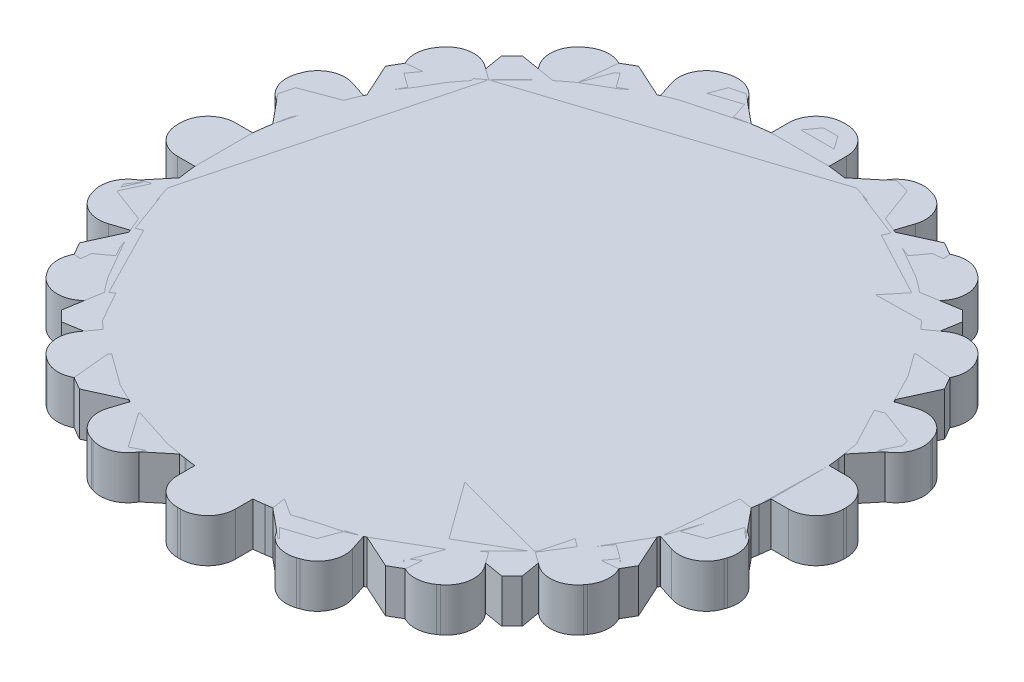
SolidWorks part; units mm, degrees
ref_plane "Front Plane" through (0, 0, 0) normal (0, 0, 1) x (1, 0, 0)
ref_plane "Top Plane" through (0, 0, 0) normal (0, 1, 0) x (1, 0, 0)
ref_plane "Right Plane" through (0, 0, 0) normal (1, 0, 0) x (0, 0, -1)
sketch "Sketch1" plane through (0, 0, 0) normal (0, 1, 0) x (1, 0, 0)
  line L111 (-0.5, 14.7462) -> (0.5, 14.7462)
  line L112 (0.5, 14.7462) -> (2, 12.5441)
  line L113 (-0.5, 14.7462) -> (-2, 12.5441)
  line L114 (6.433, 12.8885) -> (6.631, 10.2315)
  line L115 (5.567, 13.3885) -> (6.433, 12.8885)
  line L116 (5.567, 13.3885) -> (3.1669, 12.2315)
  line L117 (10.6423, 8.3132) -> (9.4853, 5.9131)
  line L118 (10.1423, 9.1792) -> (10.6423, 8.3132)
  line L119 (10.1423, 9.1792) -> (7.4853, 9.3772)
  line L120 (12, 2.2462) -> (9.798, 0.7462)
  line L121 (12, 3.2462) -> (12, 2.2462)
  line L122 (12, 3.2462) -> (9.798, 4.7462)
  line L123 (10.1423, -3.6868) -> (7.4853, -3.8849)
  line L124 (10.6423, -2.8208) -> (10.1423, -3.6868)
  line L125 (10.6423, -2.8208) -> (9.4853, -0.4208)
  line L126 (5.567, -7.8961) -> (3.1669, -6.7391)
  line L127 (6.433, -7.3961) -> (5.567, -7.8961)
  line L128 (6.433, -7.3961) -> (6.631, -4.7391)
  line L129 (-0.5, -9.2538) -> (-2, -7.0518)
  line L130 (0.5, -9.2538) -> (-0.5, -9.2538)
  line L131 (0.5, -9.2538) -> (2, -7.0518)
  line L132 (-6.433, -7.3961) -> (-6.631, -4.7391)
  line L133 (-5.567, -7.8961) -> (-6.433, -7.3961)
  line L134 (-5.567, -7.8961) -> (-3.1669, -6.7391)
  line L135 (-10.6423, -2.8208) -> (-9.4853, -0.4208)
  line L136 (-10.1423, -3.6868) -> (-10.6423, -2.8208)
  line L137 (-10.1423, -3.6868) -> (-7.4853, -3.8849)
  line L138 (-12, 3.2462) -> (-9.798, 4.7462)
  line L139 (-12, 2.2462) -> (-12, 3.2462)
  line L140 (-12, 2.2462) -> (-9.798, 0.7462)
  line L141 (-10.1423, 9.1792) -> (-7.4853, 9.3772)
  line L142 (-10.6423, 8.3132) -> (-10.1423, 9.1792)
  line L143 (-10.6423, 8.3132) -> (-9.4853, 5.9131)
  line L144 (-5.567, 13.3885) -> (-3.1669, 12.2315)
  line L145 (-6.433, 12.8885) -> (-5.567, 13.3885)
  line L146 (-6.433, 12.8885) -> (-6.631, 10.2315)
  arc A43 (-2, 12.5441) -> (-3.1669, 12.2315) centre (0, 2.7462) ccw
  arc A44 (-6.631, 10.2315) -> (-7.4853, 9.3772) centre (0, 2.7462) ccw
  arc A45 (-9.4853, 5.9131) -> (-9.798, 4.7462) centre (0, 2.7462) ccw
  arc A46 (-9.798, 0.7462) -> (-9.4853, -0.4208) centre (0, 2.7462) ccw
  arc A47 (-7.4853, -3.8849) -> (-6.631, -4.7391) centre (0, 2.7462) ccw
  arc A48 (-3.1669, -6.7391) -> (-2, -7.0518) centre (0, 2.7462) ccw
  arc A49 (2, -7.0518) -> (3.1669, -6.7391) centre (0, 2.7462) ccw
  arc A50 (6.631, -4.7391) -> (7.4853, -3.8849) centre (0, 2.7462) ccw
  arc A51 (9.4853, -0.4208) -> (9.798, 0.7462) centre (0, 2.7462) ccw
  arc A52 (9.798, 4.7462) -> (9.4853, 5.9131) centre (0, 2.7462) ccw
  arc A53 (7.4853, 9.3772) -> (6.631, 10.2315) centre (0, 2.7462) ccw
  arc A54 (3.1669, 12.2315) -> (2, 12.5441) centre (0, 2.7462) ccw
  point P6 (0, 0)
  point P8 (0, 0)
  point P9 (0, 0)
  point P12 (0, 2.7462)
  point P17 (0, 0)
  point P18 (0, 2.7462)
  point P22 (-2.5, 0.7462)
  point P63 (0, 0)
  point P68 (0, 0)
  point P69 (0, 2.7462)
  point P119 (0, 0)
  dimension "D1" = 20
  dimension "D8" = 12
sketch "Sketch2" plane through (0, 0, 0) normal (0, 1, 0) x (1, 0, 0)
  line L0 (-2, 0) -> (2, 0)
  line L1 (-23, -0.1) -> (-23, 0.1)
  line L2 (-21.1, 2) -> (-19.8997, 2)
  line L3 (-21.1, -2) -> (-19.8997, -2)
  line L4 (-20.6853, 4.6181) -> (-19.5438, 4.2472)
  line L5 (-19.4493, 8.4224) -> (-18.3078, 8.0515)
  line L6 (-21.9052, 7.0123) -> (-21.8434, 7.2025)
  line L7 (-18.2458, 10.7842) -> (-17.2748, 10.0787)
  line L8 (-15.8947, 14.0203) -> (-14.9237, 13.3148)
  line L9 (-18.6662, 13.4382) -> (-18.5486, 13.6)
  line L10 (-14.0203, 15.8947) -> (-13.3148, 14.9237)
  line L11 (-10.7842, 18.2458) -> (-10.0787, 17.2748)
  line L12 (-13.6, 18.5486) -> (-13.4382, 18.6662)
  line L13 (-8.4224, 19.4493) -> (-8.0515, 18.3078)
  line L14 (-4.6181, 20.6853) -> (-4.2472, 19.5438)
  line L15 (-7.2025, 21.8434) -> (-7.0123, 21.9052)
  line L16 (-2, 21.1) -> (-2, 19.8997)
  line L17 (2, 21.1) -> (2, 19.8997)
  line L18 (-0.1, 23) -> (0.1, 23)
  line L19 (4.6181, 20.6853) -> (4.2472, 19.5438)
  line L20 (8.4224, 19.4493) -> (8.0515, 18.3078)
  line L21 (7.0123, 21.9052) -> (7.2025, 21.8434)
  line L22 (10.7842, 18.2458) -> (10.0787, 17.2748)
  line L23 (14.0203, 15.8947) -> (13.3148, 14.9237)
  line L24 (13.4382, 18.6662) -> (13.6, 18.5486)
  line L25 (15.8947, 14.0203) -> (14.9237, 13.3148)
  line L26 (18.2458, 10.7842) -> (17.2748, 10.0787)
  line L27 (18.5486, 13.6) -> (18.6662, 13.4382)
  line L28 (19.4493, 8.4224) -> (18.3078, 8.0515)
  line L29 (20.6853, 4.6181) -> (19.5438, 4.2472)
  line L30 (21.8434, 7.2025) -> (21.9052, 7.0123)
  line L31 (21.1, 2) -> (19.8997, 2)
  line L32 (21.1, -2) -> (19.8997, -2)
  line L33 (23, 0.1) -> (23, -0.1)
  line L34 (20.6853, -4.6181) -> (19.5438, -4.2472)
  line L35 (19.4493, -8.4224) -> (18.3078, -8.0515)
  line L36 (21.9052, -7.0123) -> (21.8434, -7.2025)
  line L37 (18.2458, -10.7842) -> (17.2748, -10.0787)
  line L38 (15.8947, -14.0203) -> (14.9237, -13.3148)
  line L39 (18.6662, -13.4382) -> (18.5486, -13.6)
  line L40 (14.0203, -15.8947) -> (13.3148, -14.9237)
  line L41 (10.7842, -18.2458) -> (10.0787, -17.2748)
  line L42 (13.6, -18.5486) -> (13.4382, -18.6662)
  line L43 (8.4224, -19.4493) -> (8.0515, -18.3078)
  line L44 (4.6181, -20.6853) -> (4.2472, -19.5438)
  line L45 (7.2025, -21.8434) -> (7.0123, -21.9052)
  line L46 (2, -21.1) -> (2, -19.8997)
  line L47 (-2, -21.1) -> (-2, -19.8997)
  line L48 (0.1, -23) -> (-0.1, -23)
  line L49 (-4.6181, -20.6853) -> (-4.2472, -19.5438)
  line L50 (-8.4224, -19.4493) -> (-8.0515, -18.3078)
  line L51 (-7.0123, -21.9052) -> (-7.2025, -21.8434)
  line L52 (-10.7842, -18.2458) -> (-10.0787, -17.2748)
  line L53 (-14.0203, -15.8947) -> (-13.3148, -14.9237)
  line L54 (-13.4382, -18.6662) -> (-13.6, -18.5486)
  line L55 (-15.8947, -14.0203) -> (-14.9237, -13.3148)
  line L56 (-18.2458, -10.7842) -> (-17.2748, -10.0787)
  line L57 (-18.5486, -13.6) -> (-18.6662, -13.4382)
  line L58 (-19.4493, -8.4224) -> (-18.3078, -8.0515)
  line L59 (-20.6853, -4.6181) -> (-19.5438, -4.2472)
  line L60 (-21.8434, -7.2025) -> (-21.9052, -7.0123)
  arc A0 (-18.3078, -8.0515) -> (-17.2748, -10.0787) centre (0, 0) ccw
  arc A1 (-21.1, 2) -> (-23, 0.1) centre (-21.1, 0.1) ccw
  arc A2 (-21.1, -2) -> (-23, -0.1) centre (-21.1, -0.1) cw
  arc A3 (-20.6853, 4.6181) -> (-21.9052, 7.0123) centre (-20.0982, 6.4252) cw
  arc A4 (-19.4493, 8.4224) -> (-21.8434, 7.2025) centre (-20.0364, 6.6154) ccw
  arc A5 (-18.2458, 10.7842) -> (-18.6662, 13.4382) centre (-17.129, 12.3214) cw
  arc A6 (-15.8947, 14.0203) -> (-18.5486, 13.6) centre (-17.0115, 12.4832) ccw
  arc A7 (-14.0203, 15.8947) -> (-13.6, 18.5486) centre (-12.4832, 17.0115) cw
  arc A8 (-10.7842, 18.2458) -> (-13.4382, 18.6662) centre (-12.3214, 17.129) ccw
  arc A9 (-8.4224, 19.4493) -> (-7.2025, 21.8434) centre (-6.6154, 20.0364) cw
  arc A10 (-4.6181, 20.6853) -> (-7.0123, 21.9052) centre (-6.4252, 20.0982) ccw
  arc A11 (-2, 21.1) -> (-0.1, 23) centre (-0.1, 21.1) cw
  arc A12 (2, 21.1) -> (0.1, 23) centre (0.1, 21.1) ccw
  arc A13 (4.6181, 20.6853) -> (7.0123, 21.9052) centre (6.4252, 20.0982) cw
  arc A14 (8.4224, 19.4493) -> (7.2025, 21.8434) centre (6.6154, 20.0364) ccw
  arc A15 (10.7842, 18.2458) -> (13.4382, 18.6662) centre (12.3214, 17.129) cw
  arc A16 (14.0203, 15.8947) -> (13.6, 18.5486) centre (12.4832, 17.0115) ccw
  arc A17 (15.8947, 14.0203) -> (18.5486, 13.6) centre (17.0115, 12.4832) cw
  arc A18 (18.2458, 10.7842) -> (18.6662, 13.4382) centre (17.129, 12.3214) ccw
  arc A19 (19.4493, 8.4224) -> (21.8434, 7.2025) centre (20.0364, 6.6154) cw
  arc A20 (20.6853, 4.6181) -> (21.9052, 7.0123) centre (20.0982, 6.4252) ccw
  arc A21 (21.1, 2) -> (23, 0.1) centre (21.1, 0.1) cw
  arc A22 (21.1, -2) -> (23, -0.1) centre (21.1, -0.1) ccw
  arc A23 (20.6853, -4.6181) -> (21.9052, -7.0123) centre (20.0982, -6.4252) cw
  arc A24 (19.4493, -8.4224) -> (21.8434, -7.2025) centre (20.0364, -6.6154) ccw
  arc A25 (18.2458, -10.7842) -> (18.6662, -13.4382) centre (17.129, -12.3214) cw
  arc A26 (15.8947, -14.0203) -> (18.5486, -13.6) centre (17.0115, -12.4832) ccw
  arc A27 (14.0203, -15.8947) -> (13.6, -18.5486) centre (12.4832, -17.0115) cw
  arc A28 (10.7842, -18.2458) -> (13.4382, -18.6662) centre (12.3214, -17.129) ccw
  arc A29 (8.4224, -19.4493) -> (7.2025, -21.8434) centre (6.6154, -20.0364) cw
  arc A30 (4.6181, -20.6853) -> (7.0123, -21.9052) centre (6.4252, -20.0982) ccw
  arc A31 (2, -21.1) -> (0.1, -23) centre (0.1, -21.1) cw
  arc A32 (-2, -21.1) -> (-0.1, -23) centre (-0.1, -21.1) ccw
  arc A33 (-4.6181, -20.6853) -> (-7.0123, -21.9052) centre (-6.4252, -20.0982) cw
  arc A34 (-8.4224, -19.4493) -> (-7.2025, -21.8434) centre (-6.6154, -20.0364) ccw
  arc A35 (-10.7842, -18.2458) -> (-13.4382, -18.6662) centre (-12.3214, -17.129) cw
  arc A36 (-14.0203, -15.8947) -> (-13.6, -18.5486) centre (-12.4832, -17.0115) ccw
  arc A37 (-15.8947, -14.0203) -> (-18.5486, -13.6) centre (-17.0115, -12.4832) cw
  arc A38 (-18.2458, -10.7842) -> (-18.6662, -13.4382) centre (-17.129, -12.3214) ccw
  arc A39 (-19.4493, -8.4224) -> (-21.8434, -7.2025) centre (-20.0364, -6.6154) cw
  arc A40 (-20.6853, -4.6181) -> (-21.9052, -7.0123) centre (-20.0982, -6.4252) ccw
  arc A41 (-19.8997, -2) -> (-19.5438, -4.2472) centre (0, 0) ccw
  arc A42 (-19.5438, 4.2472) -> (-19.8997, 2) centre (0, 0) ccw
  arc A43 (-17.2748, 10.0787) -> (-18.3078, 8.0515) centre (0, 0) ccw
  arc A44 (-13.3148, 14.9237) -> (-14.9237, 13.3148) centre (0, 0) ccw
  arc A45 (-8.0515, 18.3078) -> (-10.0787, 17.2748) centre (0, 0) ccw
  arc A46 (-2, 19.8997) -> (-4.2472, 19.5438) centre (0, 0) ccw
  arc A47 (4.2472, 19.5438) -> (2, 19.8997) centre (0, 0) ccw
  arc A48 (10.0787, 17.2748) -> (8.0515, 18.3078) centre (0, 0) ccw
  arc A49 (14.9237, 13.3148) -> (13.3148, 14.9237) centre (0, 0) ccw
  arc A50 (18.3078, 8.0515) -> (17.2748, 10.0787) centre (0, 0) ccw
  arc A51 (19.8997, 2) -> (19.5438, 4.2472) centre (0, 0) ccw
  arc A52 (19.5438, -4.2472) -> (19.8997, -2) centre (0, 0) ccw
  arc A53 (17.2748, -10.0787) -> (18.3078, -8.0515) centre (0, 0) ccw
  arc A54 (13.3148, -14.9237) -> (14.9237, -13.3148) centre (0, 0) ccw
  arc A55 (8.0515, -18.3078) -> (10.0787, -17.2748) centre (0, 0) ccw
  arc A56 (2, -19.8997) -> (4.2472, -19.5438) centre (0, 0) ccw
  arc A57 (-10.0787, -17.2748) -> (-8.0515, -18.3078) centre (0, 0) ccw
  arc A58 (-4.2472, -19.5438) -> (-2, -19.8997) centre (0, 0) ccw
  arc A59 (-14.9237, -13.3148) -> (-13.3148, -14.9237) centre (0, 0) ccw
  point P6 (0, 0)
  point P10 (-23, 2)
  point P170 (0, 0)
  dimension "D1" = 40
  dimension "D4" = 1.9
  dimension "D5" = 20
extrude "Boss-Extrude3" add sketch "Sketch2" along normal blind 3 contours L55 A59 L53 A36 L54 A35 L52 A57 L50 A34 L51 A33 L49 A58 L47 A32 L48 A31 L46 A56 L44 A30 L45 A29 L43 A55 L41 A28 L42 A27 L40 A54 L38 A26 L39 A25 L37 A53 L35 A24 L36 A23 L34 A52 L32 A22 L33 A21 region at (-22.3495, 0, 0)
sketch "Sketch3" plane through (0, 0, 0) normal (0, 1, 0) x (1, 0, 0)
  line L0 (-22, 0) -> (22, 0)
  line L1 (22, -0.5) -> (22, 0.5)
  line L2 (22, 0.5) -> (19.8997, 2)
  line L3 (22, -0.5) -> (19.8997, -2)
  line L4 (21.3798, -5.2111) -> (19.7393, -3.2186)
  line L5 (21.121, -6.177) -> (21.3798, -5.2111)
  line L6 (21.121, -6.177) -> (18.704, -7.0823)
  line L7 (19.3026, -10.567) -> (18.2337, -8.2178)
  line L8 (18.8026, -11.433) -> (19.3026, -10.567)
  line L9 (18.8026, -11.433) -> (16.2337, -11.6819)
  line L10 (15.9099, -15.2028) -> (15.4855, -12.657)
  line L11 (15.2028, -15.9099) -> (15.9099, -15.2028)
  line L12 (15.2028, -15.9099) -> (12.657, -15.4855)
  line L13 (11.433, -18.8026) -> (11.6819, -16.2337)
  line L14 (10.567, -19.3026) -> (11.433, -18.8026)
  line L15 (10.567, -19.3026) -> (8.2178, -18.2337)
  line L16 (6.177, -21.121) -> (7.0823, -18.704)
  line L17 (5.2111, -21.3798) -> (6.177, -21.121)
  line L18 (5.2111, -21.3798) -> (3.2186, -19.7393)
  line L19 (0.5, -22) -> (2, -19.8997)
  line L20 (-0.5, -22) -> (0.5, -22)
  line L21 (-0.5, -22) -> (-2, -19.8997)
  line L22 (-5.2111, -21.3798) -> (-3.2186, -19.7393)
  line L23 (-6.177, -21.121) -> (-5.2111, -21.3798)
  line L24 (-6.177, -21.121) -> (-7.0823, -18.704)
  line L25 (-10.567, -19.3026) -> (-8.2178, -18.2337)
  line L26 (-11.433, -18.8026) -> (-10.567, -19.3026)
  line L27 (-11.433, -18.8026) -> (-11.6819, -16.2337)
  line L28 (-15.2028, -15.9099) -> (-12.657, -15.4855)
  line L29 (-15.9099, -15.2028) -> (-15.2028, -15.9099)
  line L30 (-15.9099, -15.2028) -> (-15.4855, -12.657)
  line L31 (-18.8026, -11.433) -> (-16.2337, -11.6819)
  line L32 (-19.3026, -10.567) -> (-18.8026, -11.433)
  line L33 (-19.3026, -10.567) -> (-18.2337, -8.2178)
  line L34 (-21.121, -6.177) -> (-18.704, -7.0823)
  line L35 (-21.3798, -5.2111) -> (-21.121, -6.177)
  line L36 (-21.3798, -5.2111) -> (-19.7393, -3.2186)
  line L37 (-22, -0.5) -> (-19.8997, -2)
  line L38 (-22, 0.5) -> (-22, -0.5)
  line L39 (-22, 0.5) -> (-19.8997, 2)
  line L40 (-21.3798, 5.2111) -> (-19.7393, 3.2186)
  line L41 (-21.121, 6.177) -> (-21.3798, 5.2111)
  line L42 (-21.121, 6.177) -> (-18.704, 7.0823)
  line L43 (-19.3026, 10.567) -> (-18.2337, 8.2178)
  line L44 (-18.8026, 11.433) -> (-19.3026, 10.567)
  line L45 (-18.8026, 11.433) -> (-16.2337, 11.6819)
  line L46 (-15.9099, 15.2028) -> (-15.4855, 12.657)
  line L47 (-15.2028, 15.9099) -> (-15.9099, 15.2028)
  line L48 (-15.2028, 15.9099) -> (-12.657, 15.4855)
  line L49 (-11.433, 18.8026) -> (-11.6819, 16.2337)
  line L50 (-10.567, 19.3026) -> (-11.433, 18.8026)
  line L51 (-10.567, 19.3026) -> (-8.2178, 18.2337)
  line L52 (-6.177, 21.121) -> (-7.0823, 18.704)
  line L53 (-5.2111, 21.3798) -> (-6.177, 21.121)
  line L54 (-5.2111, 21.3798) -> (-3.2186, 19.7393)
  line L55 (-0.5, 22) -> (-2, 19.8997)
  line L56 (0.5, 22) -> (-0.5, 22)
  line L57 (0.5, 22) -> (2, 19.8997)
  line L58 (5.2111, 21.3798) -> (3.2186, 19.7393)
  line L59 (6.177, 21.121) -> (5.2111, 21.3798)
  line L60 (6.177, 21.121) -> (7.0823, 18.704)
  line L61 (10.567, 19.3026) -> (8.2178, 18.2337)
  line L62 (11.433, 18.8026) -> (10.567, 19.3026)
  line L63 (11.433, 18.8026) -> (11.6819, 16.2337)
  line L64 (15.2028, 15.9099) -> (12.657, 15.4855)
  line L65 (15.9099, 15.2028) -> (15.2028, 15.9099)
  line L66 (15.9099, 15.2028) -> (15.4855, 12.657)
  line L67 (18.8026, 11.433) -> (16.2337, 11.6819)
  line L68 (19.3026, 10.567) -> (18.8026, 11.433)
  line L69 (19.3026, 10.567) -> (18.2337, 8.2178)
  line L70 (21.121, 6.177) -> (18.704, 7.0823)
  line L71 (21.3798, 5.2111) -> (21.121, 6.177)
  line L72 (21.3798, 5.2111) -> (19.7393, 3.2186)
  arc A0 (-8.2178, -18.2337) -> (-7.0823, -18.704) centre (0, 0) ccw
  arc A1 (-12.657, -15.4855) -> (-11.6819, -16.2337) centre (0, 0) ccw
  arc A2 (-16.2337, -11.6819) -> (-15.4855, -12.657) centre (0, 0) ccw
  arc A3 (-18.704, -7.0823) -> (-18.2337, -8.2178) centre (0, 0) ccw
  arc A4 (-19.8997, -2) -> (-19.7393, -3.2186) centre (0, 0) ccw
  arc A5 (-19.7393, 3.2186) -> (-19.8997, 2) centre (0, 0) ccw
  arc A6 (-18.2337, 8.2178) -> (-18.704, 7.0823) centre (0, 0) ccw
  arc A7 (-15.4855, 12.657) -> (-16.2337, 11.6819) centre (0, 0) ccw
  arc A8 (-11.6819, 16.2337) -> (-12.657, 15.4855) centre (0, 0) ccw
  arc A9 (-7.0823, 18.704) -> (-8.2178, 18.2337) centre (0, 0) ccw
  arc A10 (-2, 19.8997) -> (-3.2186, 19.7393) centre (0, 0) ccw
  arc A11 (3.2186, 19.7393) -> (2, 19.8997) centre (0, 0) ccw
  arc A12 (8.2178, 18.2337) -> (7.0823, 18.704) centre (0, 0) ccw
  arc A13 (12.657, 15.4855) -> (11.6819, 16.2337) centre (0, 0) ccw
  arc A14 (16.2337, 11.6819) -> (15.4855, 12.657) centre (0, 0) ccw
  arc A15 (18.704, 7.0823) -> (18.2337, 8.2178) centre (0, 0) ccw
  arc A16 (19.8997, 2) -> (19.7393, 3.2186) centre (0, 0) ccw
  arc A17 (19.7393, -3.2186) -> (19.8997, -2) centre (0, 0) ccw
  arc A18 (18.2337, -8.2178) -> (18.704, -7.0823) centre (0, 0) ccw
  arc A19 (-3.2186, -19.7393) -> (-2, -19.8997) centre (0, 0) ccw
  arc A20 (2, -19.8997) -> (3.2186, -19.7393) centre (0, 0) ccw
  arc A21 (7.0823, -18.704) -> (8.2178, -18.2337) centre (0, 0) ccw
  arc A22 (11.6819, -16.2337) -> (12.657, -15.4855) centre (0, 0) ccw
  arc A23 (15.4855, -12.657) -> (16.2337, -11.6819) centre (0, 0) ccw
  point P6 (0, 0)
  point P7 (0, -12.952)
  point P8 (-6.2727, 0)
  point P9 (11.4668, 0)
  point P10 (0, 0)
  point P108 (0, 0)
  dimension "D1" = 40
  dimension "D2" = 22
  dimension "D3" = 2
  dimension "D4" = 24
extrude "Boss-Extrude5" add sketch "Sketch3" along normal blind 3 separate body contours L2 A16 L72 L71 L70 A15 L69 L68 L67 A14 L66 L65 L64 A13 L63 L62 L61 A12 L60 L59 L58 A11 L57 L56 L55 A10 L54 L53 L52 A9 L51 L50 L49 A8 L48 L47 L46 A7 L45 L44 L43 A6 L42 L41 L40 A5 L39 L38 L0 L1 | L10 A23 L9 L8 L7 A18 L6 L5 L4 A17 L3 L1 L0 L38 L37 A4 L36 L35 L34 A3 L33 L32 L31 A2 L30 L29 L28 A1 L27 L26 L25 A0 L24 L23 L22 A19 L21 L20 L19 A20 L18 L17 L16 A21 L15 L14 L13 A22 L12 L11 region at (0, 0, -8.8989) region at (0, 0, 8.8989)
extrude "Boss-Extrude6" add sketch "Sketch1" along normal blind 3 separate body
sketch "Sketch4" plane through (0, 3, 0) normal (0, 1, 0) x (1, 0, 0)
  circle A0 centre (0, 0) radius 4.125
  dimension "D1" = 8.25
extrude "Cut-Extrude1" cut sketch "Sketch4" against normal blind 10
